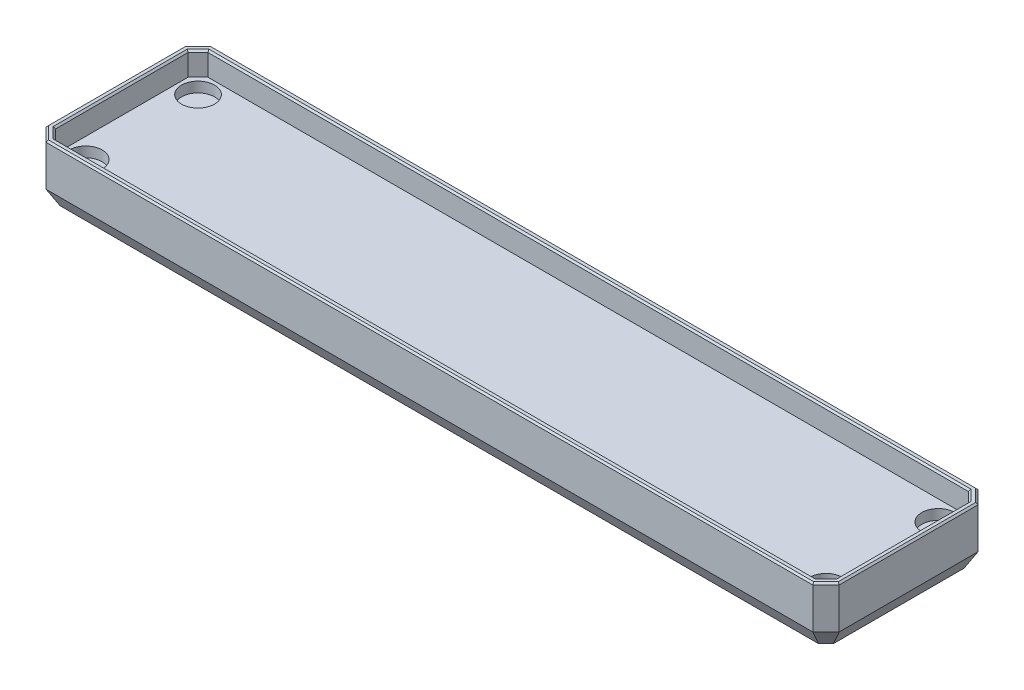
SolidWorks part; units mm, degrees
ref_plane "Front Plane" through (0, 0, 0) normal (0, 0, 1) x (1, 0, 0)
ref_plane "Top Plane" through (0, 0, 0) normal (0, 1, 0) x (1, 0, 0)
ref_plane "Right Plane" through (0, 0, 0) normal (1, 0, 0) x (0, 0, -1)
sketch "Sketch1" plane through (0, 0, 0) normal (0, 1, 0) x (1, 0, 0)
  line L0 (98.96, 31.66) -> (0, 31.66) construction
  line L1 (0, 0) -> (230, 0)
  line L2 (0, 0) -> (0, 40)
  line L3 (0, 40) -> (230, 40)
  line L4 (230, 0) -> (230, 40)
  line L5 (260, 0) -> (260, 40) construction
  line L10 (-5, 45) -> (235, 45)
  line L11 (-5, 45) -> (-5, -5)
  line L12 (-5, -5) -> (235, -5)
  line L13 (235, 45) -> (235, -5)
  line L14 (260, 20) -> (-5, 20) construction
  dimension "D3" = 5
  dimension "D4" = 5
  dimension "D5" = 5
  dimension "D1" = 40
  dimension "D2" = 230
  dimension "D6" = 5
  dimension "D7" = 30
extrude "Boss-Extrude1" add sketch "Sketch1" against normal blind 11 contours L11 L10 L13 L12
sketch "Sketch6" plane through (0, 0, 0) normal (0, 1, 0) x (1, 0, 0)
  line L1 (-3, 43) -> (233, 43) construction
  line L2 (-3, 43) -> (-3, -3) construction
  line L3 (-3, -3) -> (233, -3) construction
  line L4 (233, 43) -> (233, -3) construction
  line L5 (-5, 45) -> (235, 45) construction
  line L6 (-5, 45) -> (-5, -5) construction
  line L7 (235, 45) -> (235, -5) construction
  line L8 (-5, -5) -> (235, -5) construction
  circle A0 centre (3, 37) radius 5
  circle A1 centre (227, 37) radius 5
  circle A2 centre (227, 3) radius 5
  circle A3 centre (3, 3) radius 5
  point P4 (3, 42)
  point P5 (-2, 37)
  point P6 (227, 42)
  point P7 (232, 37)
  point P18 (232, 42)
  point P19 (-2, 42)
  point P20 (227, -2)
  point P21 (232, -2)
  point P28 (232, 3)
  point P29 (3, -2)
  point P30 (-2, 3)
  point P31 (-2, -2)
  dimension "D5" = 10
  dimension "D1" = 2
  dimension "D2" = 2
  dimension "D3" = 2
  dimension "D4" = 2
  dimension "D7" = 1
  dimension "D12" = 1
  dimension "D13" = 1
  dimension "D10" = 1
  dimension "D11" = 1
  dimension "D8" = 1
  dimension "D9" = 1
  dimension "D6" = 1
chamfer "Chamfer5" distance 4 angle 45 4 edges at (235, -5.5, 5) (-5, -5.5, 5) (-5, -5.5, -45) (235, -5.5, -45)
extrude "Cut-Extrude5" cut sketch "Sketch6" against normal blind 3.1
chamfer "Chamfer9" distance 3 angle 60 8 edges at (-3, -11, 3) (115, -11, 5) (233, -11, 3) (235, -11, -20) (233, -11, -43) (115, -11, -45) (-3, -11, -43) (-5, -11, -20) first distance on face at (115, -11, -20)
sketch "Sketch8" plane through (0, 0, 0) normal (0, 1, 0) x (1, 0, 0)
  line L0 (-3.05, -0.05) -> (-0.05, -3.05)
  line L1 (-0.05, -3.05) -> (230.05, -3.05)
  line L2 (-3.05, -0.05) -> (-3.05, 40.05)
  line L3 (-0.05, 43.05) -> (230.05, 43.05)
  line L4 (233.05, -0.05) -> (233.05, 40.05)
  line L5 (-3.05, 40.05) -> (-0.05, 43.05)
  line L6 (230.05, 43.05) -> (233.05, 40.05)
  line L11 (230.05, -3.05) -> (233.05, -0.05)
  line L16 (-5, 41) -> (-1, 45)
  line L17 (-1, 45) -> (231, 45)
  line L18 (231, 45) -> (235, 41)
  line L19 (235, 41) -> (235, -1)
  line L20 (235, -1) -> (231, -5)
  line L21 (231, -5) -> (-1, -5)
  line L22 (-1, -5) -> (-5, -1)
  line L23 (-5, -1) -> (-5, 41)
  point P0 (-3.05, -3.05)
  point P1 (233.05, 43.05)
  point P2 (-3.05, 43.05)
  point P3 (233.05, -3.05)
  dimension "D2" = 1.95
  dimension "D3" = 1.95
  dimension "D4" = 1.95
  dimension "D5" = 1.95
  dimension "D6" = 3
  dimension "D7" = 3
extrude "Boss-Extrude4" add sketch "Sketch8" along normal blind 7
chamfer "Chamfer13" distance 0.5 angle 45 8 edges at (231.55, 7, 1.55) (115, 7, 3.05) (-1.55, 7, 1.55) (231.55, 7, -41.55) (115, 7, -43.05) (-1.55, 7, -41.55) (-3.05, 7, -20) (233.05, 7, -20)
ref_axis "Axis3" through (-5, 7, 1) along (0, -1, 0)
chamfer "Chamfer14" distance 0.5 angle 45 8 edges at (-3, 7, 3) (115, 7, 5) (233, 7, 3) (235, 7, -20) (233, 7, -43) (115, 7, -45) (-3, 7, -43) (-5, 7, -20)
sketch "Sketch10" plane through (0, 0, 0) normal (0, 1, 0) x (1, 0, 0)
  line L0 (230.55, 11.6246) -> (230.55, 27.416)
  line L1 (-3.05, 8) -> (233.05, 8) construction
  line L2 (233.05, 32) -> (-3.05, 32) construction
  line L3 (-0.55, 12.577) -> (-0.55, 28.3685)
  line L4 (222, 43.05) -> (222, -3.05) construction
  line L5 (8, -3.05) -> (8, 43.05) construction
  line L6 (217.416, 40.55) -> (11.195, 40.55)
  line L7 (218.4022, -0.55) -> (12.577, -0.55)
  line L8 (233.05, 9.4) -> (222, 9.4) construction
  line L9 (220.6, 8) -> (220.6, -3.05) construction
  line L10 (9.4, -3.05) -> (9.4, 8) construction
  line L11 (8, 9.4) -> (-3.05, 9.4) construction
  line L12 (233.05, 30.6) -> (222, 30.6) construction
  line L13 (221.0112, 43.05) -> (221.0112, 32) construction
  line L14 (9.3669, 32) -> (9.3669, 43.05) construction
  line L15 (8, 30.6) -> (-3.05, 30.6) construction
  line L16 (233.05, -0.05) -> (233.05, 40.05) construction
  line L17 (-0.05, -3.05) -> (230.05, -3.05) construction
  line L18 (230.05, 43.05) -> (-0.05, 43.05) construction
  line L21 (-3.05, 40.05) -> (-3.05, -0.05) construction
  circle A0 centre (3, 37) radius 6.4 construction
  circle A2 centre (227, 37) radius 6.4 construction
  circle A3 centre (3, 3) radius 6.4 construction
  arc A4 (3, 30.6) -> (9.3669, 37.65) centre (3, 37) ccw
  arc A5 (227.3667, 30.6105) -> (220.6105, 37.3667) centre (227, 37) cw
  arc A6 (220.6, 3) -> (227, 9.4) centre (227, 3) cw
  arc A7 (3, 9.4) -> (9.4, 3) centre (3, 3) cw
  circle A15 centre (3, 3) radius 5 construction
  circle A16 centre (227, 3) radius 5 construction
  circle A17 centre (227, 37) radius 5 construction
  circle A18 centre (3, 37) radius 5 construction
  circle A19 centre (227, 3) radius 6.4 construction
  dimension "D6" = 12.8
  dimension "D7" = 12.8
  dimension "D8" = 12.8
  dimension "D9" = 12.8
  dimension "D1" = 2.5
  dimension "D2" = 2.5
  dimension "D3" = 2.5
  dimension "D4" = 2.5
  dimension "D5" = 5.4
equation "\"D3@Sketch1\" = \"Wall Thickness\""
equation "\"D4@Sketch1\" = \"Wall Thickness\""
equation "\"D5@Sketch1\" = \"Wall Thickness\""
equation "\"D1@Boss-Extrude1\"=11"
equation "\"D6@Sketch1\" = \"Wall Thickness\""
equation "\"D2@Sketch6\" = \"Female Fit Wall Thickness\""
equation "\"D1@Sketch6\" = \"Female Fit Wall Thickness\""
equation "\"D4@Sketch6\" = \"Female Fit Wall Thickness\""
equation "\"D3@Sketch6\" = \"Female Fit Wall Thickness\""
equation "\"D1@Cut-Extrude5\"= \"Magnet Height\""
equation "\"D7@Sketch6\" = \"Magnet Clearance to Corner\""
equation "\"D12@Sketch6\" = \"Magnet Clearance to Corner\""
equation "\"D13@Sketch6\" = \"Magnet Clearance to Corner\""
equation "\"D10@Sketch6\" = \"Magnet Clearance to Corner\""
equation "\"D11@Sketch6\" = \"Magnet Clearance to Corner\""
equation "\"D8@Sketch6\"= \"Magnet Clearance to Corner\""
equation "\"D9@Sketch6\" = \"Magnet Clearance to Corner\""
equation "\"Male to Female Fit Horizontal Tolerance\"= 0.05"
equation "\"Male Fit Wall Thickness\"= \"Female Fit Wall Thickness\" - \"Male to Female Fit Horizontal Tolerance\""
equation "\"D2@Sketch8\"=\"Male Fit Wall Thickness\""
equation "\"D3@Sketch8\"=\"Male Fit Wall Thickness\""
equation "\"D4@Sketch8\"=\"Male Fit Wall Thickness\""
equation "\"D5@Sketch8\"=\"Male Fit Wall Thickness\""
equation "\"Magnet Clearance to Corner\"= 1"
equation "\"D6@Sketch6\"=\"Magnet Clearance to Corner\""
equation "\"Magnet Diameter\"= 10"
equation "\"Magnet Height\"= 3.1"
equation "\"D5@Sketch6\"=\"Magnet Diameter\""
equation "\"D1@Boss-Extrude4\" = \"Female Fit Wall Height\""
equation "\"Female Fit Internal Chamfer\"= 3"
equation "\"Male Fit External Chamfer\"= \"Female Fit Internal Chamfer\""
equation "\"D6@Sketch8\" = \"Male Fit External Chamfer\""
equation "\"D7@Sketch8\"=\"Male Fit External Chamfer\""
equation "\"Wall Thickness\"= 5"
equation "\"Mouse X\"= 98.96"
equation "\"Mouse Y\"= 63.25"
equation "\"Mouse Z\"= 33.90"
equation "\"Fabric Tolerance\"= 1.5"
equation "\"Female Fit Wall Thickness\"= 2"
equation "\"Female Fit Wall Height\"= 7"
equation "\"Screw Head Diameter\"= 8.6"
equation "\"Screw Head Height\"= 3.6"
equation "\"Screw Tail Diameter\"= 4.9"
equation "\"Screw Tail Length\"= 16"
equation "\"Screw Clearance to Corner\"= 1.4"
equation "\"Bottom Mouse Negative Depth\"= 12"
